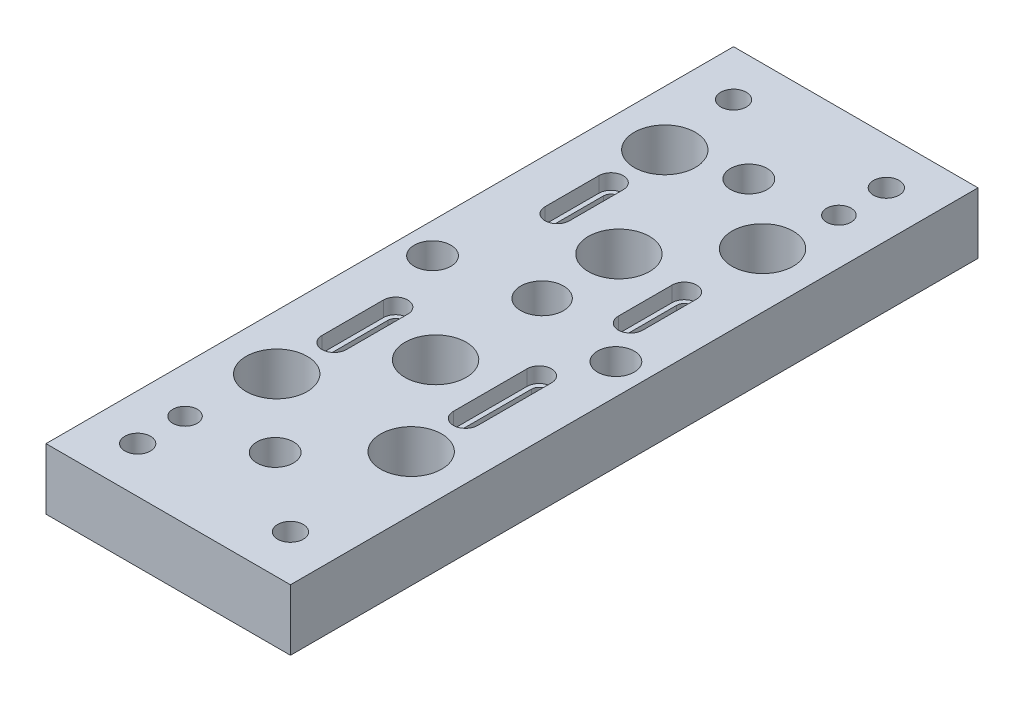
SolidWorks part; units mm, degrees
material "Plain Carbon Steel"
ref_plane "Front Plane" through (0, 0, 0) normal (0, 0, 1) x (1, 0, 0)
ref_plane "Top Plane" through (0, 0, 0) normal (0, 1, 0) x (1, 0, 0)
ref_plane "Right Plane" through (0, 0, 0) normal (1, 0, 0) x (0, 0, -1)
sketch "Sketch1" plane through (0, 0, 0) normal (0, 1, 0) x (1, 0, 0)
  line L1 (-40, -112.5) -> (40, -112.5)
  line L2 (-40, -112.5) -> (-40, 112.5)
  line L3 (-40, 112.5) -> (40, 112.5)
  line L4 (40, -112.5) -> (40, 112.5)
  line L5 (-40, -112.5) -> (40, 112.5) construction
  line L6 (-40, 112.5) -> (40, -112.5) construction
  point P0 (0, 0)
  dimension "D1" = 225
  dimension "D2" = 80
extrude "Boss-Extrude1" add sketch "Sketch1" against normal blind 20
sketch "Sketch2" plane through (0, 0, 0) normal (0, 1, 0) x (1, 0, 0)
  line L4 (24, 17.31) -> (24, 34.91)
  line L5 (19, 34.91) -> (19, 17.31)
  line L6 (24, 17.31) -> (24, 34.91)
  line L7 (19, 34.91) -> (19, 17.31)
  line L10 (24, -36.69) -> (24, -12.59)
  line L11 (19, -12.59) -> (19, -36.69)
  line L12 (24, -36.69) -> (24, -12.59)
  line L13 (19, -12.59) -> (19, -36.69)
  line L16 (-24, -16.59) -> (-24, -36.69)
  line L17 (-19, -36.69) -> (-19, -16.59)
  line L18 (-24, -16.59) -> (-24, -36.69)
  line L19 (-19, -36.69) -> (-19, -16.59)
  line L22 (-24, 53.91) -> (-24, 36.31)
  line L23 (-19, 36.31) -> (-19, 53.91)
  line L24 (-24, 53.91) -> (-24, 36.31)
  line L25 (-19, 36.31) -> (-19, 53.91)
  arc A4 (24, 34.91) -> (19, 34.91) centre (21.5, 34.91) ccw
  arc A5 (19, 17.31) -> (24, 17.31) centre (21.5, 17.31) ccw
  arc A6 (24, 34.91) -> (19, 34.91) centre (21.5, 34.91) ccw
  arc A7 (19, 17.31) -> (24, 17.31) centre (21.5, 17.31) ccw
  arc A10 (24, -12.59) -> (19, -12.59) centre (21.5, -12.59) ccw
  arc A11 (19, -36.69) -> (24, -36.69) centre (21.5, -36.69) ccw
  arc A12 (24, -12.59) -> (19, -12.59) centre (21.5, -12.59) ccw
  arc A13 (19, -36.69) -> (24, -36.69) centre (21.5, -36.69) ccw
  arc A16 (-24, -36.69) -> (-19, -36.69) centre (-21.5, -36.69) ccw
  arc A17 (-19, -16.59) -> (-24, -16.59) centre (-21.5, -16.59) ccw
  arc A18 (-24, -36.69) -> (-19, -36.69) centre (-21.5, -36.69) ccw
  arc A19 (-19, -16.59) -> (-24, -16.59) centre (-21.5, -16.59) ccw
  arc A22 (-24, 36.31) -> (-19, 36.31) centre (-21.5, 36.31) ccw
  arc A23 (-19, 53.91) -> (-24, 53.91) centre (-21.5, 53.91) ccw
  arc A24 (-24, 36.31) -> (-19, 36.31) centre (-21.5, 36.31) ccw
  arc A25 (-19, 53.91) -> (-24, 53.91) centre (-21.5, 53.91) ccw
  dimension "D2" = 0.05
  dimension "D1" = 0.05
  dimension "D3" = 0.05
  dimension "D4" = 0.05
extrude "Cut-Extrude1" cut sketch "Sketch2" against normal up to next
sketch "Sketch3" plane through (0, 0, 0) normal (0, 1, 0) x (1, 0, 0)
  line L4 (-17.5, 36.31) -> (-17.5, 53.91)
  line L5 (-25.5, 53.91) -> (-25.5, 36.31)
  line L6 (-17.5, 36.31) -> (-17.5, 53.91)
  line L7 (-25.5, 53.91) -> (-25.5, 36.31)
  line L10 (25.5, 17.31) -> (25.5, 34.91)
  line L11 (17.5, 34.91) -> (17.5, 17.31)
  line L12 (25.5, 17.31) -> (25.5, 34.91)
  line L13 (17.5, 34.91) -> (17.5, 17.31)
  line L16 (25.5, -36.69) -> (25.5, -12.59)
  line L17 (17.5, -12.59) -> (17.5, -36.69)
  line L18 (25.5, -36.69) -> (25.5, -12.59)
  line L19 (17.5, -12.59) -> (17.5, -36.69)
  line L22 (-25.5, -16.59) -> (-25.5, -36.69)
  line L23 (-17.5, -36.69) -> (-17.5, -16.59)
  line L24 (-25.5, -16.59) -> (-25.5, -36.69)
  line L25 (-17.5, -36.69) -> (-17.5, -16.59)
  arc A4 (-17.5, 53.91) -> (-25.5, 53.91) centre (-21.5, 53.91) ccw
  arc A5 (-25.5, 36.31) -> (-17.5, 36.31) centre (-21.5, 36.31) ccw
  arc A6 (-17.5, 53.91) -> (-25.5, 53.91) centre (-21.5, 53.91) ccw
  arc A7 (-25.5, 36.31) -> (-17.5, 36.31) centre (-21.5, 36.31) ccw
  arc A10 (25.5, 34.91) -> (17.5, 34.91) centre (21.5, 34.91) ccw
  arc A11 (17.5, 17.31) -> (25.5, 17.31) centre (21.5, 17.31) ccw
  arc A12 (25.5, 34.91) -> (17.5, 34.91) centre (21.5, 34.91) ccw
  arc A13 (17.5, 17.31) -> (25.5, 17.31) centre (21.5, 17.31) ccw
  arc A16 (25.5, -12.59) -> (17.5, -12.59) centre (21.5, -12.59) ccw
  arc A17 (17.5, -36.69) -> (25.5, -36.69) centre (21.5, -36.69) ccw
  arc A18 (25.5, -12.59) -> (17.5, -12.59) centre (21.5, -12.59) ccw
  arc A19 (17.5, -36.69) -> (25.5, -36.69) centre (21.5, -36.69) ccw
  arc A22 (-25.5, -36.69) -> (-17.5, -36.69) centre (-21.5, -36.69) ccw
  arc A23 (-17.5, -16.59) -> (-25.5, -16.59) centre (-21.5, -16.59) ccw
  arc A24 (-25.5, -36.69) -> (-17.5, -36.69) centre (-21.5, -36.69) ccw
  arc A25 (-17.5, -16.59) -> (-25.5, -16.59) centre (-21.5, -16.59) ccw
  dimension "D1" = 1.5
  dimension "D2" = 1.5
  dimension "D3" = 1.5
  dimension "D4" = 1.5
extrude "Cut-Extrude2" cut sketch "Sketch3" against normal blind 5
hole_wizard "CBORE for M8 Hex Socket Head Cap Screw1" positions "Sketch7" profile "Sketch6" counterbore size "M8" standard "ISO" end condition through all
sketch "Sketch7" plane through (0, -20, 0) normal (0, -1, 0) x (-1, 0, 0)
  line L0 (-40, -112.5) -> (-40, 112.5) construction
  line L1 (-40, 112.5) -> (40, 112.5) construction
  line L2 (40, 112.5) -> (40, -112.5) construction
  line L3 (40, -112.5) -> (-40, -112.5) construction
  point P0 (-25, 97.5)
  point P2 (25, 97.5)
  point P4 (25, -97.5)
  point P6 (-25, -97.5)
  dimension "D1" = 15
  dimension "D2" = 15
  dimension "D3" = 15
  dimension "D4" = 15
sketch "Sketch6" plane through (25, -20, -97.5) normal (1, 0, 0) x (0, 0, -1)
  line L0 (0, 0) -> (0, 20)
  line L1 (0, 20) -> (4.2, 20)
  line L3 (4.2, 20) -> (4.2, 8.6)
  line L4 (7.5, 8.6) -> (4.2, 8.6)
  line L5 (7.5, 8.6) -> (7.5, 0.025)
  line L6 (7.5, 0.025) -> (7.525, 0)
  line L7 (7.525, 0) -> (0, 0)
  line L8 (-7.5, 0.025) -> (-7.525, 0) construction
  line L11 (0, -6.35) -> (0, 107.95) construction
  dimension "Thru Hole Dia." = 8.4
  dimension "Thru Hole Depth" = 20
  dimension "C'Bore Dia." = 15
  dimension "C'Bore Depth" = 8.6
  dimension "Near C'Sink Dia." = 15.05
  dimension "Near C'Sink Angle" = 90
hole_wizard "Ø8.0mm Dowel Hole1" positions "Sketch12" profile "Sketch9" hole size "Ø8.0" standard "ISO" end condition through all
sketch "Sketch12" plane through (0, -20, 0) normal (0, -1, 0) x (-1, 0, 0)
  line L4 (25, -97.5) -> (25, -82) construction
  line L6 (-25, 97.5) -> (-25, 81.975) construction
  circle A1 centre (25, -97.5) radius 7.5 construction
  circle A3 centre (-25, 97.5) radius 7.525 construction
  point P0 (-25, 81.975)
  point P2 (25, -82)
  dimension "D1" = 8
  dimension "D2" = 8
sketch "Sketch9" plane through (25, -20, -81.975) normal (1, 0, 0) x (0, 0, -1)
  line L0 (0, 0) -> (0, 20)
  line L1 (0, 20) -> (4, 20)
  line L2 (4, 20) -> (4, 0)
  line L5 (4, 0) -> (0, 0)
  line L11 (0, -6.35) -> (0, 107.95) construction
  dimension "Thru Hole Dia." = 8
  dimension "Thru Hole Depth" = 20
sketch "Sketch11" plane through (0, -20, 0) normal (0, -1, 0) x (1, 0, 0)
  circle A0 centre (-22, 55) radius 10
  circle A1 centre (22, 55) radius 10
  circle A2 centre (-22, -72) radius 10
  circle A3 centre (22, -60) radius 10
  circle A4 centre (0, -35) radius 10
  circle A5 centre (0, 25) radius 10
  dimension "D1" = 20
  dimension "D2" = 35
  dimension "D3" = 25
  dimension "D4" = 72
  dimension "D5" = 22
  dimension "D6" = 22
  dimension "D7" = 55
  dimension "D8" = 60
extrude "Cut-Extrude3" cut sketch "Sketch11" against normal through all
sketch "Sketch13" plane through (0, 0, 0) normal (0, 1, 0) x (1, 0, 0)
  circle A0 centre (0, 77.5) radius 6
  circle A1 centre (0, -77.5) radius 6
  circle A2 centre (-30, 4) radius 6
  circle A3 centre (30, 4) radius 6
  dimension "D1" = 12
extrude "Cut-Extrude4" cut sketch "Sketch13" against normal up to next
sketch "Sketch14" plane through (0, 0, 0) normal (0, 1, 0) x (1, 0, 0)
  circle A0 centre (0, 9.86) radius 5 construction
  circle A1 centre (0, 9.86) radius 5 construction
  circle A2 centre (0, 9.86) radius 7
  dimension "D1" = 14
extrude "Cut-Extrude5" cut sketch "Sketch14" against normal up to next
